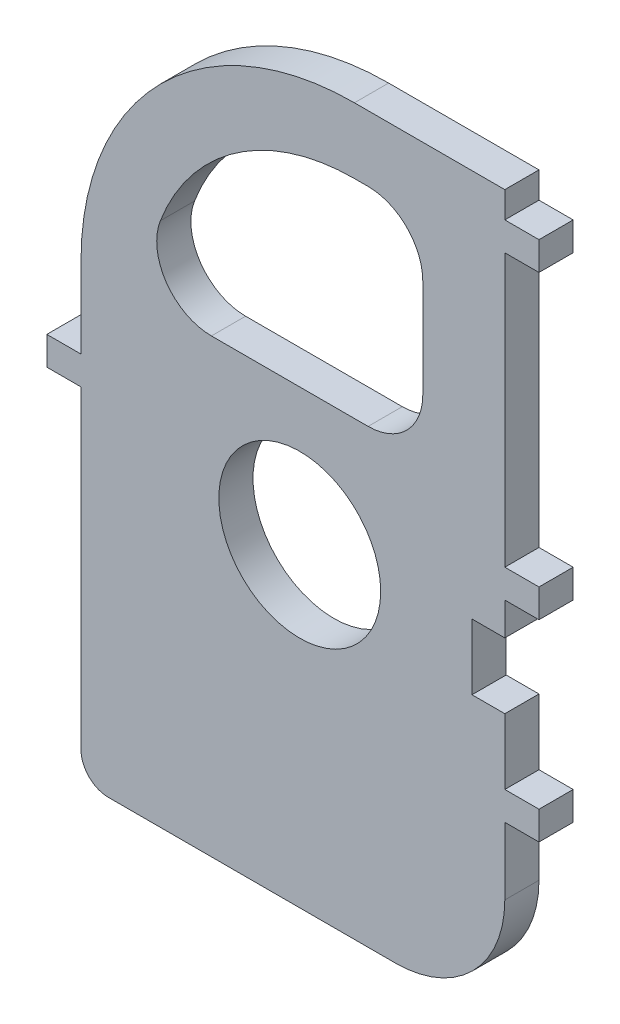
SolidWorks part; units mm, degrees
material "Balsa"
ref_plane "Front Plane" through (0, 0, 0) normal (0, 0, 1) x (1, 0, 0)
ref_plane "Top Plane" through (0, 0, 0) normal (0, 1, 0) x (1, 0, 0)
ref_plane "Right Plane" through (0, 0, 0) normal (1, 0, 0) x (0, 0, -1)
sketch "Sketch1" plane through (0, 0, 0) normal (0, 0, 1) x (1, 0, 0)
  line L0 (0, -1000.1535) -> (0, 48999.8465) construction
  line L2 (-1000, 0) -> (49000, 0) construction
  line L3 (9.525, 16.51) -> (11.1125, 16.51)
  line L4 (2.54, 19.05) -> (9.525, 19.05)
  line L5 (-10.16, 6.35) -> (-10.16, -14.605)
  line L6 (-10.16, -14.605) -> (9.525, -14.605)
  line L7 (9.525, 19.05) -> (9.525, -14.605)
  line L8 (-11.7475, 1.27) -> (-10.16, 1.27)
  line L9 (-11.7475, 1.27) -> (-11.7475, 2.5908)
  line L10 (-11.7475, 2.5908) -> (-10.16, 2.5908)
  line L11 (-10.16, 1.27) -> (-10.16, 2.5908)
  line L12 (9.525, 2.54) -> (11.1125, 2.54)
  line L13 (9.525, 2.54) -> (9.525, 3.8608)
  line L14 (9.525, 3.8608) -> (11.1125, 3.8608)
  line L15 (11.1125, 2.54) -> (11.1125, 3.8608)
  line L16 (9.525, 16.51) -> (9.525, 17.8308)
  line L17 (9.525, 17.8308) -> (11.1125, 17.8308)
  line L18 (11.1125, 16.51) -> (11.1125, 17.8308)
  line L19 (9.525, -5.08) -> (11.1125, -5.08)
  line L20 (9.525, -5.08) -> (9.525, -6.4008)
  line L21 (9.525, -6.4008) -> (11.1125, -6.4008)
  line L22 (11.1125, -5.08) -> (11.1125, -6.4008)
  line L27 (9.525, 1.016) -> (8.001, 1.016)
  line L28 (9.525, 1.016) -> (9.525, -2.032)
  line L29 (9.525, -2.032) -> (8.001, -2.032)
  line L30 (8.001, 1.016) -> (8.001, -2.032)
  circle A0 centre (0, 0) radius 3.7592
  arc A3 (2.54, 19.05) -> (-10.16, 6.35) centre (2.54, 6.35) ccw
  dimension "D1" = 7.5184
  dimension "D4" = 14.605
  dimension "D3" = 16.51
  dimension "D5" = 1.5875
  dimension "D9" = 12.7
  dimension "D10" = 1.5875
  dimension "D18" = 1.27
  dimension "D2" = 19.05
  dimension "D6" = 9.525
  dimension "D7" = 1.3208
  dimension "D8" = 19.685
  dimension "D11" = 2.54
  dimension "D12" = 1.3208
  dimension "D13" = 1.3208
  dimension "D14" = 1.5875
  dimension "D15" = 1.524
  dimension "D16" = 1.016
  dimension "D17" = 3.048
  dimension "D19" = 1.5875
  dimension "D20" = 1.3208
  dimension "D21" = 5.08
extrude "Boss-Extrude1" add sketch "Sketch1" along normal blind 1.5875 contours L4 A3 L5 L6 L7 A0 | L10 L9 L8 L5 | L3 L18 L17 L7 | L12 L15 L14 L7 | A3 L5 | L22 L19 L7 L21 region at (10.3187, 17.1704, 0) region at (9.1351, 10.1854, 0) region at (10.3187, 3.2004, 0) region at (-10.9538, 1.9304, 0) region at (10.3187, -5.7404, 0)
fillet "Fillet1" radius 5.08 1 edges at (9.525, -14.605, 0.7937)
fillet "Fillet2" radius 1.27 1 edges at (-10.16, -14.605, 0.7937)
sketch "Sketch2" plane through (0, 0, 1.5875) normal (0, 0, 1) x (1, 0, 0)
  line L0 (-7.112, 6.35) -> (5.715, 6.35)
  line L1 (5.715, 16.002) -> (2.54, 16.002)
  line L2 (5.715, 16.002) -> (5.715, 6.35)
  line L3 (9.525, 16.51) -> (9.525, 3.8608) construction
  arc A2 (2.54, 16.002) -> (-7.112, 6.35) centre (2.54, 6.35) ccw
  arc A3 (2.54, 16.002) -> (-7.112, 6.35) centre (2.54, 6.35) ccw
  dimension "D2" = 3.81
  dimension "D1" = 3.048
extrude "Weight Reduction" cut sketch "Sketch2" against normal up to next
fillet "Fillet3" radius 2.54 3 edges at (-7.112, 6.35, 0.7937) (5.715, 16.002, 0.7937) (5.715, 6.35, 0.7937)
